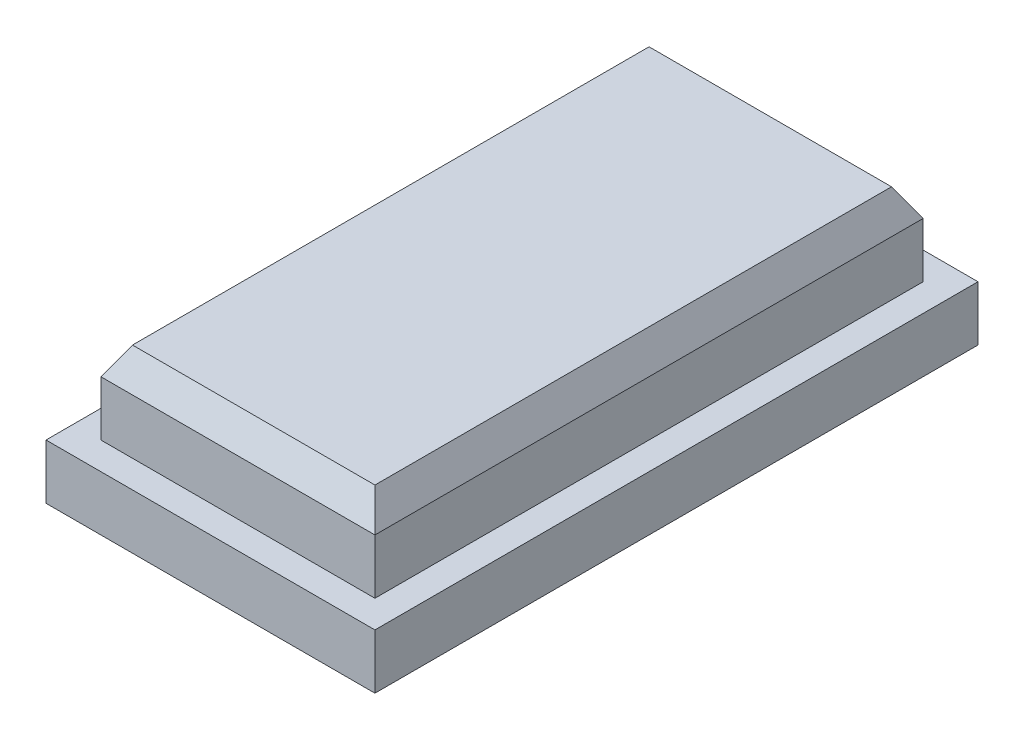
SolidWorks part; units mm, degrees
ref_plane "Спереди" through (0, 0, 0) normal (0, 0, 1) x (1, 0, 0)
ref_plane "Сверху" through (0, 0, 0) normal (0, 1, 0) x (1, 0, 0)
ref_plane "Справа" through (0, 0, 0) normal (1, 0, 0) x (0, 0, -1)
sketch "Sketch1" plane through (0, 0, 0) normal (0, 1, 0) x (1, 0, 0)
  line L1 (6, -11) -> (-6, -11)
  line L2 (6, -11) -> (6, 11)
  line L3 (6, 11) -> (-6, 11)
  line L4 (-6, -11) -> (-6, 11)
  line L5 (6, -11) -> (-6, 11) construction
  line L6 (6, 11) -> (-6, -11) construction
  point P0 (0, 0)
  dimension "D1" = 12
  dimension "D2" = 22
extrude "Boss-Extrude1" add sketch "Sketch1" along normal blind 2
sketch "Sketch2" plane through (0, 2, 0) normal (0, 1, 0) x (1, 0, 0)
  line L1 (5, -10) -> (-5, -10)
  line L2 (5, -10) -> (5, 10)
  line L3 (5, 10) -> (-5, 10)
  line L4 (-5, -10) -> (-5, 10)
  line L5 (5, -10) -> (-5, 10) construction
  line L6 (5, 10) -> (-5, -10) construction
  point P0 (0, 0)
  point P5 (0, 0)
  dimension "D1" = 10
  dimension "D2" = 20
extrude "Boss-Extrude2" add sketch "Sketch2" along normal blind 3
chamfer "Chamfer1" distance 1 angle 30 4 edges at (0, 5, -10) (5, 5, 0) (0, 5, 10) (-5, 5, 0) first distance on face at (0, 3.5, -10) first distance on face at (5, 3.5, 0) first distance on face at (0, 3.5, 10) first distance on face at (-5, 3.5, 0)
